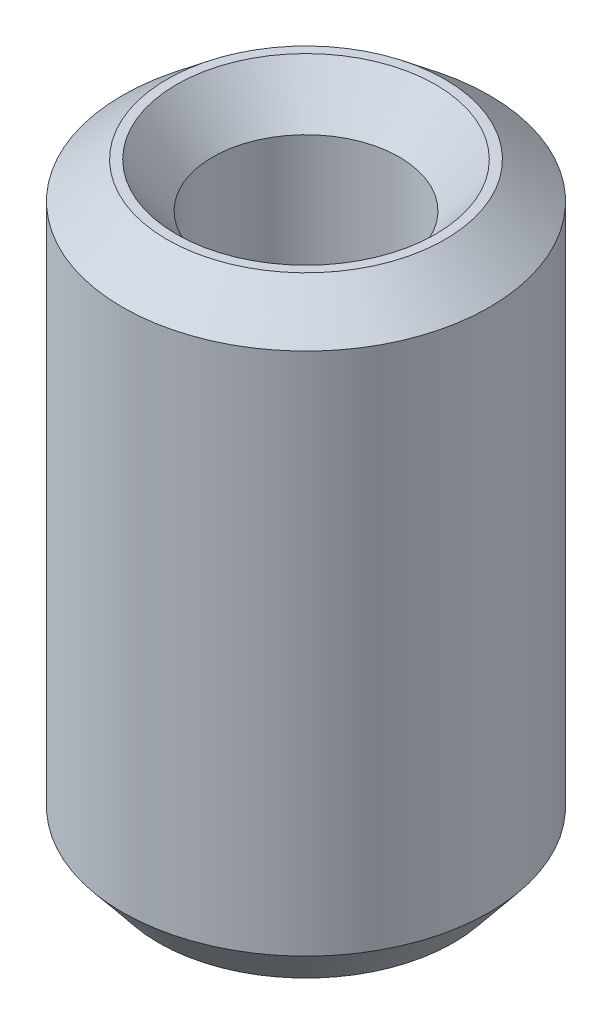
SolidWorks part; units mm, degrees
ref_plane "Front Plane" through (0, 0, 0) normal (0, 0, 1) x (1, 0, 0)
ref_plane "Top Plane" through (0, 0, 0) normal (0, 1, 0) x (1, 0, 0)
ref_plane "Right Plane" through (0, 0, 0) normal (1, 0, 0) x (0, 0, -1)
sketch "Sketch1" plane through (0, 0, 0) normal (0, 1, 0) x (1, 0, 0)
  circle A0 centre (0, 0) radius 7.5
  dimension "SLEEVE_OD" = 15
extrude "Boss-Extrude1" add sketch "Sketch1" along normal blind 24.7197
sketch "Sketch2" plane through (0, 0, 0) normal (0, 1, 0) x (1, 0, 0)
  circle A0 centre (0, 0) radius 3.8147
  dimension "BORE_D" = 7.6295
extrude "Cut-Extrude1" cut sketch "Sketch2" along normal through all
chamfer "Chamfer1" distance 1.4822 angle 50.885 4 edges at (0, 24.7197, 3.8147) (0, 0, 3.8147) (0, 0, 7.5) (0, 24.7197, 7.5) first distance on face at (0, 24.7197, 3.8147) first distance on face at (0, 0, 3.8147) first distance on face at (0, 24.7197, 7.5)
